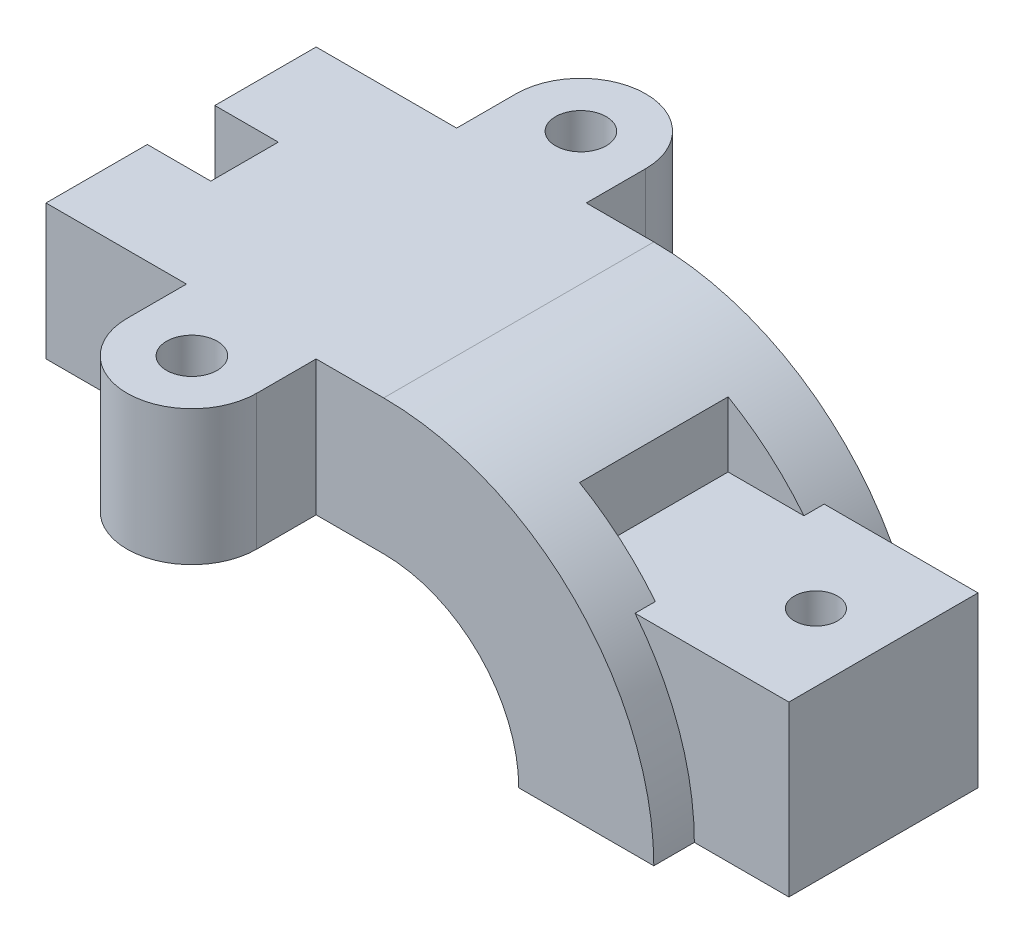
SolidWorks part; units mm, degrees
ref_plane "Front Plane" through (0, 0, 0) normal (0, 0, 1) x (1, 0, 0)
ref_plane "Top Plane" through (0, 0, 0) normal (0, 1, 0) x (1, 0, 0)
ref_plane "Right Plane" through (0, 0, 0) normal (1, 0, 0) x (0, 0, -1)
sketch "Sketch1" plane through (0, 0, 0) normal (0, 0, 1) x (1, 0, 0)
  line L0 (25.4, 0) -> (50.8, 0)
  line L1 (-63.5, 25.4) -> (-63.5, 50.8)
  line L2 (0, 25.4) -> (-63.5, 25.4)
  line L3 (0, 50.8) -> (-63.5, 50.8)
  line L4 (50.8, 0) -> (68.58, 0)
  line L5 (68.58, 0) -> (68.58, 31.75)
  line L6 (68.58, 31.75) -> (25.4, 31.75)
  line L7 (25.4, 0) -> (25.4, 31.75)
  line L8 (25.4, 31.75) -> (25.4, 43.9941)
  line L9 (25.4, 31.75) -> (-63.5, 31.75)
  line L10 (-51.562, 50.8) -> (-51.562, 25.4)
  arc A0 (25.4, 0) -> (0, 25.4) centre (0, 0) ccw
  arc A1 (50.8, 0) -> (0, 50.8) centre (0, 0) ccw
  dimension "D1" = 50.8
  dimension "D2" = 101.6
  dimension "D3" = 63.5
  dimension "D4" = 17.78
  dimension "D5" = 31.75
  dimension "D6" = 11.938
extrude "Boss-Extrude1" add sketch "Sketch1" along normal blind 6.35 contours A0 L7 L9 L10 L2 | L8 A1 L3 L10 L9 | L0 A1 L6 L7 | A1 L4 L5 L6 region at (36.5754, 14.5619, 0) region at (-5.8384, 26.6216, 0) region at (57.6735, 17.222, 0) region at (-14.3602, 40.9769, 0)
extrude "Boss-Extrude2" add sketch "Sketch1<3>" along normal blind 7.62 from vertex contours L8 A1 L3 L10 L9 | A0 L7 L9 L10 L2 | L10 L3 L1 L9 | L0 A1 L6 L7 | A1 L4 L5 L6 | L10 L9 L1 L2 region at (36.5754, 14.5619, 0) region at (-5.8384, 26.6216, 0) region at (57.6735, 17.222, 0) region at (-14.3602, 40.9769, 0) region at (-57.531, 28.575, 0) region at (-57.531, 41.275, 0) starting at point (-51.562, 50.8, 6.35)
sketch "Sketch1<3>" plane through (0, 0, 0) normal (0, 0, 1) x (1, 0, 0) same geometry as "Sketch1"
extrude "Boss-Extrude3" add sketch "Sketch1<7>" along normal blind 3.81 from vertex contours L8 A1 L3 L10 L9 | A0 L7 L9 L10 L2 | L0 A1 L6 L7 | L6 A1 L8 | L10 L3 L1 L9 | L10 L9 L1 L2 | A1 L4 L5 L6 region at (36.5754, 14.5619, 0) region at (-5.8384, 26.6216, 0) region at (57.6735, 17.222, 0) region at (30.4434, 36.0896, 0) region at (-14.3602, 40.9769, 0) region at (-57.531, 28.575, 0) region at (-57.531, 41.275, 0) starting at point (-63.5, 50.8, 13.97)
sketch "Sketch1<7>" plane through (0, 0, 0) normal (0, 0, 1) x (1, 0, 0) same geometry as "Sketch1"
extrude "Boss-Extrude4" add sketch "Sketch1<10>" along normal blind 7.62 from vertex contours L8 A1 L3 L10 L9 | A0 L7 L9 L10 L2 | L10 L9 L1 L2 | L10 L3 L1 L9 | L6 A1 L8 | L0 A1 L6 L7 region at (36.5754, 14.5619, 0) region at (-5.8384, 26.6216, 0) region at (30.4434, 36.0896, 0) region at (-14.3602, 40.9769, 0) region at (-57.531, 28.575, 0) region at (-57.531, 41.275, 0) starting at point (-63.5, 50.8, 17.78)
sketch "Sketch1<10>" plane through (0, 0, 0) normal (0, 0, 1) x (1, 0, 0) same geometry as "Sketch1"
mirror "Mirror7" about plane through (0, 0, 0) normal (0, 0, 1) of "Boss-Extrude2", "Boss-Extrude4", "Boss-Extrude3", "Boss-Extrude1"
sketch "Sketch2" plane through (0, 50.8, 0) normal (0, 1, 0) x (1, 0, 0)
  line L0 (-51.562, 0) -> (0, 0) construction
  line L1 (-51.562, -6.35) -> (-51.562, 6.35) construction
  line L2 (-24.892, -25.4) -> (-24.892, 25.4) construction
  line L3 (0, 25.4) -> (-63.5, 25.4) construction
  line L4 (-63.5, 25.4) -> (-63.5, 6.35) construction
  line L5 (-12.7, 36.576) -> (-12.7, 25.4)
  line L6 (-37.084, 36.576) -> (-37.084, 25.4)
  line L7 (-37.084, 25.4) -> (-12.7, 25.4)
  line L8 (-37.084, -25.4) -> (-12.7, -25.4)
  line L9 (-37.084, -36.576) -> (-37.084, -25.4)
  line L10 (-12.7, -36.576) -> (-12.7, -25.4)
  circle A0 centre (-24.892, 36.576) radius 4.7625
  arc A1 (-20.0194, 25.4) -> (-29.7646, 25.4) centre (-24.892, 36.576) ccw
  arc A2 (-20.0194, -25.4) -> (-29.7646, -25.4) centre (-24.892, -36.576) cw
  circle A3 centre (-24.892, -36.576) radius 4.7625
  point P20 (-24.892, 0)
  line M2 (0, 25.4) -> (-63.5, 25.4)
  line M8 (-63.5, -25.4) -> (0, -25.4)
  dimension "D2" = 9.525
  dimension "D3" = 24.384
  dimension "D1" = 38.608
  dimension "D4" = 11.176
extrude "Boss-Extrude5" add sketch "Sketch2" against normal up to surface (25.4 mm away) contours A2 L10 M8 | A2 L8 A3 | L9 A2 M8 | A1 L5 M2 | A1 L7 A0 | A1 L6 M2 region at (-14.7064, 50.8, -28.0004) region at (-14.9752, 50.8, -30.0813) region at (-35.0776, 50.8, -28.0004) region at (-35.0776, 50.8, 28.0004) region at (-24.892, 50.8, 25.7377) region at (-14.7064, 50.8, 28.0004) up to face at (-43.1482, 25.4, 0.7937)
sketch "Sketch3" plane through (0, 31.75, 0) normal (0, 1, 0) x (1, 0, 0)
  line L0 (68.58, -17.78) -> (68.58, 17.78) construction
  circle A0 centre (55.88, 0) radius 4.064
  dimension "D2" = 8.128
  dimension "D1" = 12.7
extrude "Cut-Extrude1" cut sketch "Sketch3" against normal through all
